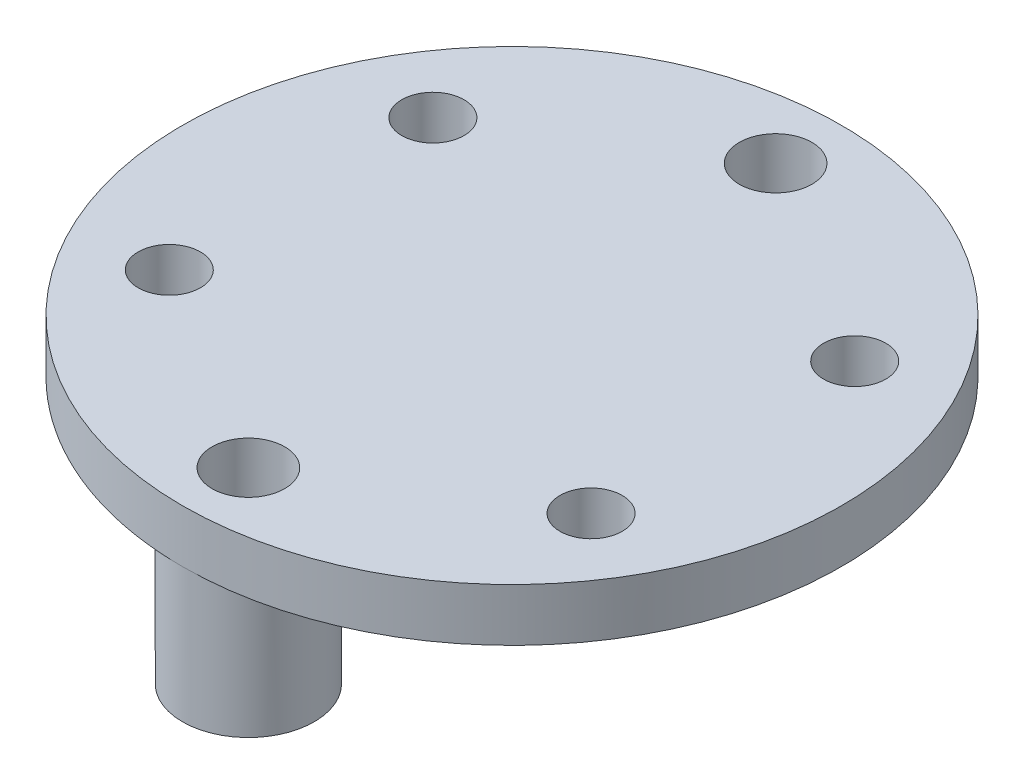
SolidWorks part; units mm, degrees
material "PLA"
ref_plane "Front Plane" through (0, 0, 0) normal (0, 0, 1) x (1, 0, 0)
ref_plane "Top Plane" through (0, 0, 0) normal (0, 1, 0) x (1, 0, 0)
ref_plane "Right Plane" through (0, 0, 0) normal (1, 0, 0) x (0, 0, -1)
sketch "Sketch1" plane through (0, 0, 0) normal (0, 1, 0) x (1, 0, 0)
  line L0 (0, 8.89) -> (0, -8.89) construction
  line L1 (-12.7, -8.89) -> (12.7, -8.89)
  line L2 (-12.7, -8.89) -> (-12.7, 8.89)
  line L3 (-12.7, 8.89) -> (12.7, 8.89)
  line L4 (12.7, -8.89) -> (12.7, 8.89)
  line L5 (-12.7, -8.89) -> (12.7, 8.89) construction
  line L6 (-12.7, 8.89) -> (12.7, -8.89) construction
  line L7 (-12.7, 0) -> (12.7, 0) construction
  circle A0 centre (0, 0) radius 15.875
  circle A1 centre (-10.16, 6.35) radius 1.5
  circle A2 centre (10.16, 6.35) radius 1.5
  circle A3 centre (10.16, -6.35) radius 1.5
  circle A4 centre (-10.16, -6.35) radius 1.5
  circle A5 centre (0, 12.7) radius 1.75
  circle A6 centre (0, -12.7) radius 1.75
  circle A7 centre (0, 12.7) radius 3.175
  circle A8 centre (0, -12.7) radius 3.175
  dimension "D1" = 31.75
  dimension "D4" = 3
  dimension "D7" = 3.5
  dimension "D2" = 17.78
  dimension "D3" = 25.4
  dimension "D5" = 12.7
  dimension "D6" = 20.32
  dimension "D8" = 12.7
extrude "Boss-Extrude1" add sketch "Sketch1" along normal blind 2.54 contours A0 A8 A7 L4 L1 L2 L3 | L1 L4 L3 L2 A2 A1 A3 A4 | A7 A5 | A8 A6 region at (0, 0, 0) region at (2.1816, 0, -14.8816) region at (-2.1816, 0, 10.5184) region at (10.9078, 0, 10.9078)
extrude "Boss-Extrude2" add sketch "Sketch1<3>" against normal blind 6.475 contours A7 A5 | A8 A6 region at (2.1816, 0, -14.8816) region at (-2.1816, 0, 10.5184)
sketch "Sketch1<3>" plane through (0, 0, 0) normal (0, 1, 0) x (1, 0, 0) same geometry as "Sketch1"
